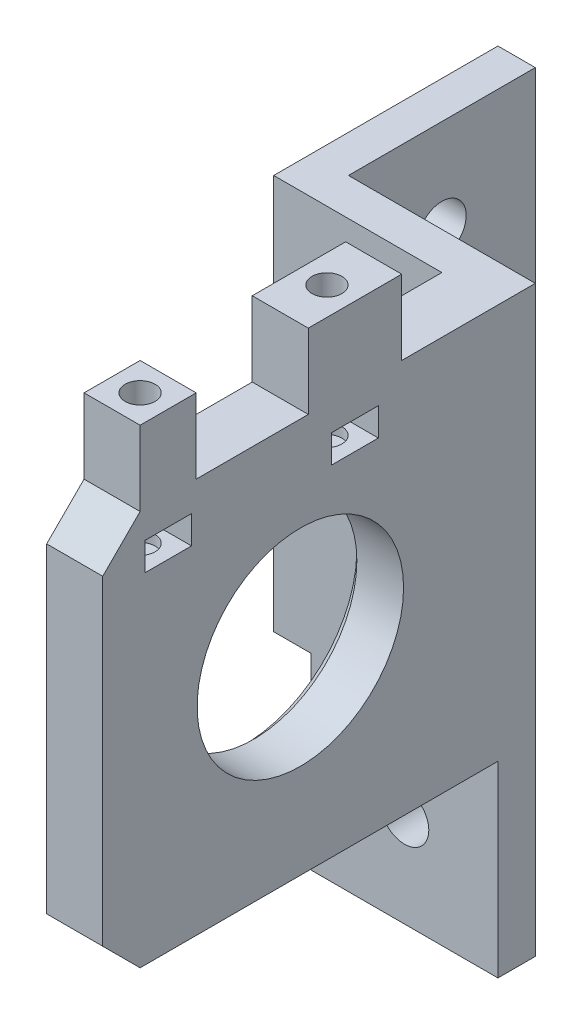
SolidWorks part; units mm, degrees
ref_plane "Přední rovina" through (0, 0, 0) normal (0, 0, 1) x (1, 0, 0)
ref_plane "Horní rovina" through (0, 0, 0) normal (0, 1, 0) x (1, 0, 0)
ref_plane "Pravá rovina" through (0, 0, 0) normal (1, 0, 0) x (0, 0, -1)
sketch "Skica2" plane through (0, 0, 0) normal (0, 0, 1) x (1, 0, 0)
  line L0 (-24.5243, -350) -> (-24.5243, 0) construction
  line L1 (-4.5243, -40) -> (-24.5243, -40)
  line L2 (-4.5243, -40) -> (-4.5243, -82.3)
  line L3 (-4.5243, -82.3) -> (-24.5243, -82.3)
  line L4 (-24.5243, -40) -> (-24.5243, -82.3)
  line L5 (-344.5243, -82.3) -> (-355.5243, -82.3) construction
extrude "Přidat vysunutím1" add sketch "Skica2" along normal blind 4
sketch "Skica3" plane through (-24.5243, 0, 0) normal (-1, 0, 0) x (0, 0, 1)
  line L0 (4, -82.3) -> (0, -82.3) construction
  line L1 (4, -40) -> (-20, -40)
  line L2 (4, -40) -> (4, -82.3)
  line L3 (4, -82.3) -> (-20, -82.3)
  line L4 (-20, -40) -> (-20, -82.3)
  line L5 (-20, -350) -> (-20, 0) construction
extrude "Přidat vysunutím2" add sketch "Skica3" along normal blind 4
sketch "Skica4" plane through (0, 0, 4) normal (0, 0, 1) x (1, 0, 0)
  line L0 (-28.5243, -82.3) -> (-4.5243, -82.3) construction
  line L1 (-10.5243, -40) -> (-4.5243, -40)
  line L2 (-10.5243, -40) -> (-10.5243, -82.3)
  line L3 (-10.5243, -82.3) -> (-4.5243, -82.3)
  line L4 (-4.5243, -40) -> (-4.5243, -82.3)
  line L5 (-4.5243, -82.3) -> (-4.5243, -40) construction
  dimension "D1" = 6
extrude "Přidat vysunutím3" add sketch "Skica4" along normal up to surface (42.3 mm away)
sketch "Skica5" plane through (-4.5243, 0, 0) normal (1, 0, 0) x (0, 0, -1)
  circle A0 centre (-25.15, -61.15) radius 11.05
  dimension "D1" = 22.1
extrude "Odebrat vysunutím1" cut sketch "Skica5" against normal blind 7
sketch "Skica7" plane through (-28.5243, 0, 0) normal (-1, 0, 0) x (0, 0, 1)
  line L0 (-20, -40) -> (-20, -82.3) construction
  line L1 (4, -40) -> (-20, -40) construction
  circle A0 centre (-10, -50) radius 2.6
  circle A1 centre (-10, -70) radius 2.6
  dimension "D3" = 5.2
  dimension "D1" = 10
  dimension "D2" = 10
  dimension "D4" = 2
extrude "Odebrat vysunutím3" cut sketch "Skica7" against normal blind 4
chamfer "Zkosení1" distance 1 angle 45 1 edges at (-10.5243, -50.1, 25.15)
sketch "Skica8" plane through (0, -82.3, 0) normal (0, -1, 0) x (1, 0, 0)
  line L0 (-28.5243, 4) -> (-10.5243, 4) construction
  line L1 (-4.5243, 0) -> (-24.5243, 0)
  line L2 (-4.5243, 0) -> (-4.5243, 4)
  line L3 (-4.5243, 4) -> (-24.5243, 4)
  line L4 (-24.5243, 0) -> (-24.5243, 4)
extrude "Přidat vysunutím4" add sketch "Skica8" along normal up to surface (20.0916 mm away)
sketch "Skica9" plane through (0, 0, 4) normal (0, 0, 1) x (1, 0, 0)
  line L0 (-24.5243, -102.3916) -> (-4.5243, -102.3916) construction
  line L1 (-4.5243, -102.3916) -> (-4.5243, -82.3) construction
  circle A0 centre (-14.5243, -92.3916) radius 2.6
  dimension "D3" = 5.2
  dimension "D1" = 10
  dimension "D2" = 10
extrude "Odebrat vysunutím4" cut sketch "Skica9" against normal blind 4
sketch "Skica10" plane through (-10.5243, 0, 0) normal (-1, 0, 0) x (0, 0, 1)
  line L0 (46.3, -44) -> (42.3, -40)
  line L1 (46.3, -40) -> (46.3, -82.3) construction
  line L2 (42.3, -40) -> (46.3, -44) construction
  line L3 (46.3, -40) -> (4, -40) construction
  line L4 (42.3, -40) -> (46.5659, -39.2593)
  line L5 (46.5659, -39.2593) -> (46.3, -44)
  line L6 (42.3, -82.3) -> (46.3, -78.3)
  line L7 (46.3, -82.3) -> (4, -82.3) construction
  line L8 (46.3, -78.3) -> (42.3, -82.3) construction
  line L9 (46.3, -78.3) -> (47.7456, -80.3)
  line L10 (47.7456, -80.3) -> (46.3, -85.4154)
  line L11 (46.3, -85.4154) -> (42.3, -82.3)
extrude "Odebrat vysunutím5" cut sketch "Skica10" against normal blind 80
sketch "Skica11" plane through (0, -40, 0) normal (0, 1, 0) x (1, 0, 0)
  line L0 (-4.5243, -42.3) -> (-4.5243, 0) construction
  line L1 (-10.5243, -42.3) -> (-4.5243, -42.3)
  line L2 (-10.5243, -42.3) -> (-10.5243, -36.3)
  line L3 (-10.5243, -36.3) -> (-4.5243, -36.3)
  line L4 (-4.5243, -42.3) -> (-4.5243, -36.3)
  line L5 (-10.5243, -42.3) -> (-10.5243, -4) construction
  line L6 (-4.5243, -24.3) -> (-10.5243, -24.3)
  line L7 (-4.5243, -24.3) -> (-4.5243, -14.3)
  line L8 (-4.5243, -14.3) -> (-10.5243, -14.3)
  line L9 (-10.5243, -24.3) -> (-10.5243, -14.3)
  line L10 (-384.5243, -36.3) -> (-4.5243, -36.3) construction
  line L11 (-384.5243, -24.3) -> (-4.5243, -24.3) construction
  dimension "D1" = 10
extrude "Přidat vysunutím5" add sketch "Skica11" along normal blind 8
sketch "Skica13" plane through (0, -32, 0) normal (0, 1, 0) x (1, 0, 0)
  line L0 (-4.5243, -42.3) -> (-4.5243, -36.3) construction
  line L1 (-4.5243, -24.3) -> (-4.5243, -14.3) construction
  circle A0 centre (-7.5243, -39.3) radius 1.6
  circle A1 centre (-7.5243, -19.3) radius 1.6
  point P7 (-4.5243, -19.3)
  point P8 (-4.5243, -39.3)
  dimension "D1" = 3.2
extrude "Odebrat vysunutím6" cut sketch "Skica13" against normal blind 15
sketch "Skica14" plane through (-4.5243, 0, 0) normal (1, 0, 0) x (0, 0, -1)
  line L0 (-39.3, -44.439) -> (-39.3, -32) construction
  line L1 (-41.8, -42.939) -> (-36.8, -42.939)
  line L2 (-41.8, -42.939) -> (-41.8, -45.939)
  line L3 (-41.8, -45.939) -> (-36.8, -45.939)
  line L4 (-36.8, -42.939) -> (-36.8, -45.939)
  line L5 (-41.8, -42.939) -> (-36.8, -45.939) construction
  line L6 (-41.8, -45.939) -> (-36.8, -42.939) construction
  line L7 (-42.3, -32) -> (-36.3, -32) construction
  line L8 (-19.3, -32) -> (-19.3, -44.439) construction
  line L9 (-24.3, -32) -> (-14.3, -32) construction
  line L11 (-16.8, -42.939) -> (-21.8, -42.939)
  line L12 (-16.8, -42.939) -> (-16.8, -45.939)
  line L13 (-16.8, -45.939) -> (-21.8, -45.939)
  line L14 (-21.8, -42.939) -> (-21.8, -45.939)
  line L15 (-16.8, -42.939) -> (-21.8, -45.939) construction
  line L16 (-16.8, -45.939) -> (-21.8, -42.939) construction
  point P0 (-39.3, -44.439)
  dimension "D1" = 5
  dimension "D2" = 3
extrude "Odebrat vysunutím7" cut sketch "Skica14" against normal blind 15
